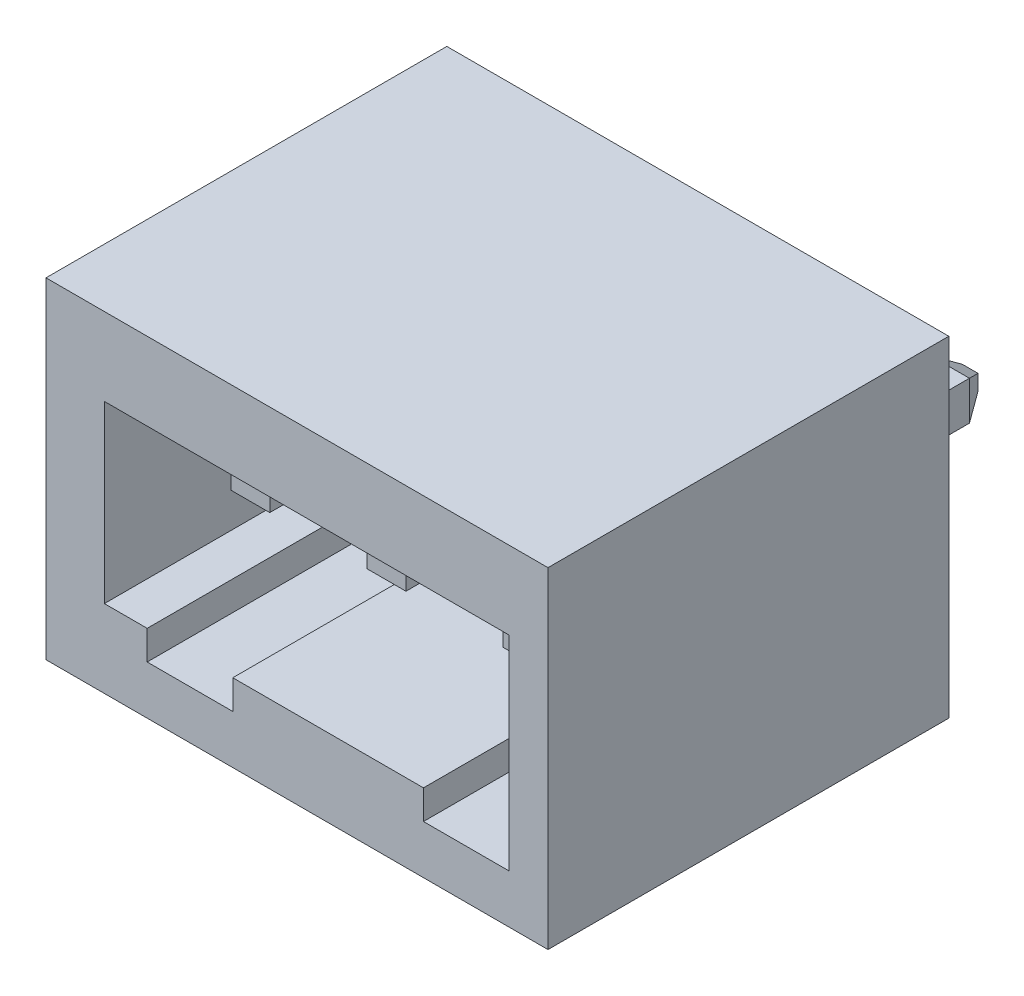
SolidWorks part; units mm, degrees
other "Детальный элемент1"
ref_plane "Спереди" through (0, 0, 0) normal (0, 0, 1) x (1, 0, 0)
ref_plane "Сверху" through (0, 0, 0) normal (0, 1, 0) x (1, 0, 0)
ref_plane "Справа" through (0, 0, 0) normal (1, 0, 0) x (0, 0, -1)
ref_axis "Ось1" through (80.9, 0, 0) along (-1, 0, 0)
sketch "Эскиз1" plane through (0, 0, 0) normal (0, 0, 1) x (1, 0, 0)
  line L0 (50, 0) -> (-50, 0) construction
  line L1 (-4, -0.5) -> (-3, -0.5)
  line L2 (-4, -0.5) -> (-4, 0.5)
  line L3 (-4, 0.5) -> (-3, 0.5)
  line L4 (-3, -0.5) -> (-3, 0.5)
  line L5 (-4, -0.5) -> (-3, 0.5) construction
  line L6 (-4, 0.5) -> (-3, -0.5) construction
  point P0 (-3.5, 0)
  dimension "D1" = 3.5
  dimension "D2" = 1
  dimension "D3" = 1
extrude "Бобышка-Вытянуть1" add sketch "Эскиз1" along normal blind 8 and the other way blind 3.5
chamfer "Фаска1" distance 0.3 angle 60 4 edges at (-3.5, -0.5, -3.5) (-4, 0, -3.5) (-3.5, 0.5, -3.5) (-3, 0, -3.5) first distance on face at (-3.5, 0, -3.5)
pattern_linear "Линейный массив1" count 3 spacing 3.5 along (1, 0, 0) of bodies 107
sketch "Эскиз3" plane through (0, 0, 0) normal (0, 0, 1) x (1, 0, 0)
  line L0 (0, -50) -> (0, 50) construction
  line L1 (6.45, 4.15) -> (-6.45, 4.15)
  line L2 (6.45, 4.15) -> (6.45, -4.35)
  line L3 (6.45, -4.35) -> (-6.45, -4.35)
  line L4 (-6.45, 4.15) -> (-6.45, -4.35)
  line L5 (6.45, 4.15) -> (-6.45, -4.35) construction
  line L6 (6.45, -4.35) -> (-6.45, 4.15) construction
  point P0 (0, -0.1)
  dimension "D1" = 8.5
  dimension "D2" = 12.9
  dimension "D3" = 4.35
extrude "Бобышка-Вытянуть2" add sketch "Эскиз3" along normal blind 10.3 separate body
shell "Оболочка1" thickness 2 removed face at (0, -0.1, 10.3)
sketch "Эскиз4" plane through (0, 0, 10.3) normal (0, 0, 1) x (1, 0, 0)
  line L0 (-4.95, -2.35) -> (5.45, -2.35) construction
  line L1 (-3.85, -2.35) -> (-1.65, -2.35)
  line L2 (-3.85, -2.35) -> (-3.85, -3.1)
  line L3 (-3.85, -3.1) -> (-1.65, -3.1)
  line L4 (-1.65, -2.35) -> (-1.65, -3.1)
  line L5 (-6.45, 4.15) -> (-6.45, -4.35) construction
  line L6 (3.25, -2.35) -> (5.45, -2.35)
  line L7 (3.25, -2.35) -> (3.25, -3.1)
  line L8 (3.25, -3.1) -> (5.45, -3.1)
  line L9 (5.45, -2.35) -> (5.45, -3.1)
  line L10 (6.45, -4.35) -> (6.45, 4.15) construction
  dimension "D1" = 2.2
  dimension "D2" = 0.75
  dimension "D3" = 4.8
  dimension "D4" = 3.2
extrude "Вырез-Вытянуть1" cut sketch "Эскиз4" against normal up to surface (8.8 mm away) up to face at (0.25, -0.1, 1.5)
